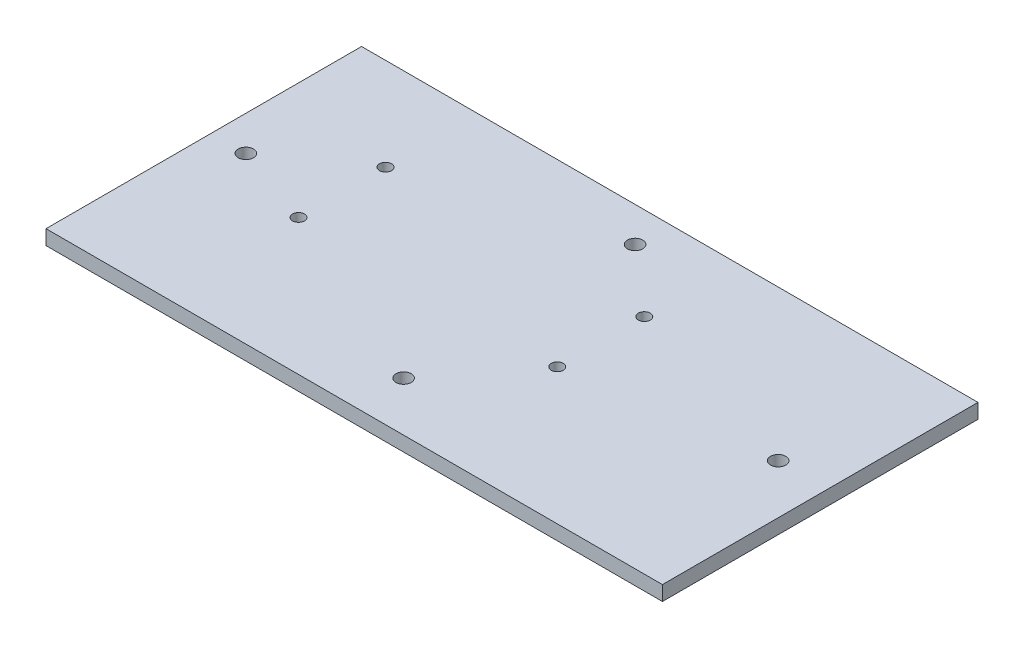
SolidWorks part; units mm, degrees
ref_plane "Front Plane" through (0, 0, 0) normal (0, 0, 1) x (1, 0, 0)
ref_plane "Top Plane" through (0, 0, 0) normal (0, 1, 0) x (1, 0, 0)
ref_plane "Right Plane" through (0, 0, 0) normal (1, 0, 0) x (0, 0, -1)
sketch "Sketch1" plane through (0, 0, 0) normal (0, 1, 0) x (1, 0, 0)
  line L0 (0, 34.0875) -> (0, -34.0875) construction
  line L1 (-66.5875, 34.0875) -> (66.5875, 34.0875)
  line L2 (-66.5875, 34.0875) -> (-66.5875, -34.0875)
  line L3 (-66.5875, -34.0875) -> (66.5875, -34.0875)
  line L4 (66.5875, 34.0875) -> (66.5875, -34.0875)
  line L5 (-66.5875, 34.0875) -> (66.5875, -34.0875) construction
  line L6 (-66.5875, -34.0875) -> (66.5875, 34.0875) construction
  line L7 (-59.0875, 26.5875) -> (55.9125, 26.5875) construction
  line L8 (-59.0875, 26.5875) -> (-59.0875, -23.4125) construction
  line L9 (-59.0875, -23.4125) -> (55.9125, -23.4125) construction
  line L10 (55.9125, 26.5875) -> (55.9125, -23.4125) construction
  line L11 (-66.5875, 0) -> (66.5875, 0) construction
  circle A0 centre (0, 26.5875) radius 1.65
  circle A1 centre (-59.0875, 1.5875) radius 1.65
  circle A2 centre (55.9125, 1.5875) radius 1.65
  circle A3 centre (0, -23.4125) radius 1.65
  point P0 (0, 0)
  point P6 (0, 0)
  dimension "D7" = 3.3
  dimension "D1" = 133.175
  dimension "D2" = 7.5
  dimension "D3" = 7.5
  dimension "D4" = 10.675
  dimension "D5" = 10.675
  dimension "D6" = 68.175
extrude "Boss-Extrude1" add sketch "Sketch1" along normal blind 3.175
sketch "Sketch2" plane through (0, 3.175, 0) normal (0, 1, 0) x (1, 0, 0)
  line L0 (66.5875, 34.0875) -> (-66.5875, 34.0875) construction
  line L1 (14.4875, -4.7125) -> (-41.4125, -4.7125) construction
  line L2 (14.4875, -4.7125) -> (14.4875, 14.0875) construction
  line L3 (14.4875, 14.0875) -> (-41.4125, 14.0875) construction
  line L4 (-41.4125, -4.7125) -> (-41.4125, 14.0875) construction
  line L5 (14.4875, -4.7125) -> (-41.4125, 14.0875) construction
  line L6 (14.4875, 14.0875) -> (-41.4125, -4.7125) construction
  line L7 (-66.5875, 34.0875) -> (-66.5875, -34.0875) construction
  circle A0 centre (14.4875, -4.7125) radius 1.3
  circle A1 centre (-41.4125, -4.7125) radius 1.3
  circle A2 centre (-41.4125, 14.0875) radius 1.3
  circle A3 centre (14.4875, 14.0875) radius 1.3
  point P0 (-13.4625, 4.6875)
  dimension "D3" = 2.6
  dimension "D1" = 55.9
  dimension "D2" = 18.8
  dimension "D4" = 20
  dimension "D5" = 25.175
extrude "Cut-Extrude1" cut sketch "Sketch2" against normal up to surface (3.175 mm away) up to face at (0, 0, 0)
